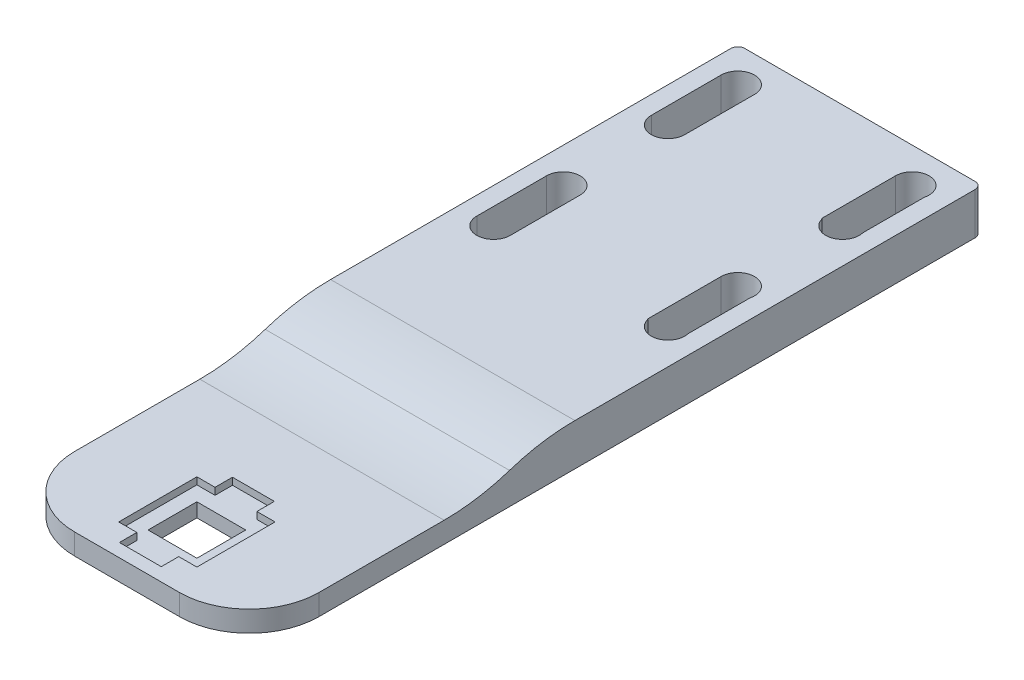
SolidWorks part; units mm, degrees
ref_plane "Front Plane" through (0, 0, 0) normal (0, 0, 1) x (1, 0, 0)
ref_plane "Top Plane" through (0, 0, 0) normal (0, 1, 0) x (1, 0, 0)
ref_plane "Right Plane" through (0, 0, 0) normal (1, 0, 0) x (0, 0, -1)
sketch "Sketch1" plane through (0, 0, 0) normal (0, 1, 0) x (1, 0, 0)
  line L1 (-17.3881, 19.9254) -> (17.6119, 19.9254)
  line L2 (-17.3881, 19.9254) -> (-17.3881, -85.0746)
  line L3 (-17.3881, -85.0746) -> (17.6119, -85.0746)
  line L4 (17.6119, 19.9254) -> (17.6119, -85.0746)
  dimension "D1" = 35
  dimension "D2" = 105
extrude "Boss-Extrude1" add sketch "Sketch1" along normal blind 6
sketch "Sketch2" plane through (0, 6, 0) normal (0, 1, 0) x (1, 0, 0)
  line L0 (17.6119, 19.9254) -> (-17.3881, 19.9254) construction
  line L1 (12.6119, -10.0746) -> (-12.3881, -10.0746)
  line L2 (12.6119, -10.0746) -> (12.6119, 14.9254)
  line L3 (12.6119, 14.9254) -> (-12.3881, 14.9254)
  line L4 (-12.3881, -10.0746) -> (-12.3881, 14.9254)
  line L5 (12.6119, -10.0746) -> (-12.3881, 14.9254) construction
  line L6 (12.6119, 14.9254) -> (-12.3881, -10.0746) construction
  point P0 (0.1119, 2.4254)
  point P7 (0.1119, 19.9254)
  dimension "D1" = 25
  dimension "D2" = 25
  dimension "D3" = 0
  dimension "D4" = 5
hole_wizard "M4 Clearance Hole1" positions "Sketch3" profile "Sketch4" hole size "M4" standard "ANSI Metric" end condition through all
sketch "Sketch3" plane through (0, 6, 0) normal (0, 1, 0) x (1, 0, 0)
  point P0 (-12.3881, 14.9254)
  point P3 (12.6119, 14.9254)
  point P6 (12.6119, -10.0746)
  point P9 (-12.3881, -10.0746)
sketch "Sketch4" plane through (-12.3881, 6, -14.9254) normal (1, 0, 0) x (0, 0, 1)
  line L0 (0, 0) -> (0, 6)
  line L1 (0, 6) -> (2.4, 6)
  line L2 (2.4, 6) -> (2.4, 0)
  line L5 (2.4, 0) -> (0, 0)
  line L11 (0, -6.35) -> (0, 107.95) construction
  dimension "Thru Hole Dia." = 4.8
  dimension "Thru Hole Depth" = 6
pattern_linear "LPattern2" count 2 spacing 10 along (0, 0, 1) of "M4 Clearance Hole1"
sketch "Sketch5" plane through (0, 6, 0) normal (0, 1, 0) x (1, 0, 0)
  line L1 (-14.7881, 14.9254) -> (-9.9881, 14.9254)
  line L2 (-14.7881, 14.9254) -> (-14.7881, 4.9254)
  line L3 (-14.7881, 4.9254) -> (-9.9881, 4.9254)
  line L4 (-9.9881, 14.9254) -> (-9.9881, 4.9254)
  line L5 (-14.7881, -10.0746) -> (-9.9881, -10.0746)
  line L6 (-14.7881, -10.0746) -> (-14.7881, -20.0746)
  line L7 (-14.7881, -20.0746) -> (-9.9881, -20.0746)
  line L8 (-9.9881, -10.0746) -> (-9.9881, -20.0746)
  line L9 (10.2119, 14.9254) -> (14.9426, 14.9254)
  line L10 (10.2119, 14.9254) -> (10.2119, 4.3527)
  line L11 (10.2119, 4.3527) -> (14.9426, 4.3527)
  line L12 (14.9426, 14.9254) -> (14.9426, 4.3527)
  line L13 (10.2119, -10.0746) -> (14.9426, -10.0746)
  line L14 (10.2119, -10.0746) -> (10.2119, -20.6473)
  line L15 (10.2119, -20.6473) -> (14.9426, -20.6473)
  line L16 (14.9426, -10.0746) -> (14.9426, -20.6473)
  circle A0 centre (-12.3881, 14.9254) radius 2.4 construction
  circle A1 centre (-12.3881, 4.9254) radius 2.4 construction
  circle A2 centre (-12.3881, -10.0746) radius 2.4 construction
  circle A3 centre (-12.3881, -20.0746) radius 2.4 construction
  circle A4 centre (12.6119, 14.9254) radius 2.4 construction
  circle A5 centre (12.6119, 4.9254) radius 2.4 construction
  circle A6 centre (12.6119, -10.0746) radius 2.4 construction
  circle A7 centre (12.6119, -20.0746) radius 2.4 construction
extrude "Cut-Extrude1" cut sketch "Sketch5" against normal through all
sketch "Sketch6" plane through (0, 6, 0) normal (0, 1, 0) x (1, 0, 0)
  line L1 (5.7119, -80.6746) -> (-5.4881, -80.6746)
  line L2 (5.7119, -80.6746) -> (5.7119, -69.4746)
  line L3 (5.7119, -69.4746) -> (-5.4881, -69.4746)
  line L4 (-5.4881, -80.6746) -> (-5.4881, -69.4746)
  line L5 (5.7119, -80.6746) -> (-5.4881, -69.4746) construction
  line L6 (5.7119, -69.4746) -> (-5.4881, -80.6746) construction
  line L9 (-17.3881, -85.0746) -> (17.6119, -85.0746) construction
  point P0 (0.1119, -75.0746)
  point P7 (0.1119, -85.0746)
  dimension "D1" = 11.2
  dimension "D2" = 11.2
  dimension "D3" = 10
  dimension "D4" = 0
extrude "Cut-Extrude2" cut sketch "Sketch6" against normal offset from surface (4 mm away) 2 up to face at (-12.3881, 0, 15.0746)
sketch "Sketch7" plane through (0, 2, 0) normal (0, 1, 0) x (1, 0, 0)
  line L0 (5.7119, -80.6746) -> (5.7119, -69.4746) construction
  line L1 (3.6119, -78.5746) -> (-3.3881, -78.5746)
  line L2 (3.6119, -78.5746) -> (3.6119, -71.5746)
  line L3 (3.6119, -71.5746) -> (-3.3881, -71.5746)
  line L4 (-3.3881, -78.5746) -> (-3.3881, -71.5746)
  line L5 (3.6119, -78.5746) -> (-3.3881, -71.5746) construction
  line L6 (3.6119, -71.5746) -> (-3.3881, -78.5746) construction
  line L7 (-17.3881, -85.0746) -> (17.6119, -85.0746) construction
  point P0 (0.1119, -75.0746)
  point P7 (5.7119, -75.0746)
  point P10 (0.1119, -85.0746)
  dimension "D1" = 0
  dimension "D2" = 0
  dimension "D3" = 7
  dimension "D4" = 7
extrude "Cut-Extrude3" cut sketch "Sketch7" against normal through all
sketch "Sketch8" plane through (0, 6, 0) normal (0, 1, 0) x (1, 0, 0)
  line L0 (5.7119, -69.4746) -> (-5.4881, -69.4746) construction
  line L1 (3.1119, -83.1746) -> (-2.8881, -83.1746)
  line L2 (3.1119, -83.1746) -> (3.1119, -66.9746)
  line L3 (3.1119, -66.9746) -> (-2.8881, -66.9746)
  line L4 (-2.8881, -83.1746) -> (-2.8881, -66.9746)
  line L5 (3.1119, -83.1746) -> (-2.8881, -66.9746) construction
  line L6 (3.1119, -66.9746) -> (-2.8881, -83.1746) construction
  line L7 (5.7119, -80.6746) -> (-5.4881, -80.6746) construction
  line L9 (3.6119, -71.5746) -> (-3.3881, -71.5746) construction
  point P0 (0.1119, -75.0746)
  point P11 (0.1119, -71.5746)
  dimension "D1" = 2.5
  dimension "D2" = 2.5
  dimension "D3" = 6
  dimension "D4" = 0
extrude "Cut-Extrude4" cut sketch "Sketch8" against normal up to surface (4 mm away) up to face at (0.1119, 2, 75.0746)
fillet "Fillet1" radius 10 2 edges at (17.6119, 3, 85.0746) (-17.3881, 3, 85.0746)
sketch "Sketch9" plane through (0, 0, 0) normal (0, -1, 0) x (1, 0, 0)
  line L0 (-17.3881, -19.9254) -> (-17.3881, 75.0746) construction
  line L1 (-17.3881, 44.0746) -> (19.6619, 44.0746)
  line L2 (-17.3881, 44.0746) -> (-17.3881, 85.0746)
  line L3 (-17.3881, 85.0746) -> (19.6619, 85.0746)
  line L4 (19.6619, 44.0746) -> (19.6619, 85.0746)
  line L5 (-7.3881, 85.0746) -> (7.6119, 85.0746) construction
  line L6 (5.7119, 69.4746) -> (3.1119, 69.4746) construction
  dimension "D1" = 25.4
  dimension "D2" = 0
extrude "Cut-Extrude5" cut sketch "Sketch9" along normal offset from surface (3 mm away) 3 from surface up to face at (0.1119, 0, 75.0746) starting at face at (0.1119, 6, 75.0746)
fillet "Fillet2" radius 30 1 edges at (0.1119, 3, 44.0746)
fillet "Fillet3" radius 30 1 edges at (0.1119, 6, 44.0746)
fillet "Fillet4" radius 1 2 edges at (17.6119, 3, -19.9254) (-17.3881, 3, -19.9254)
